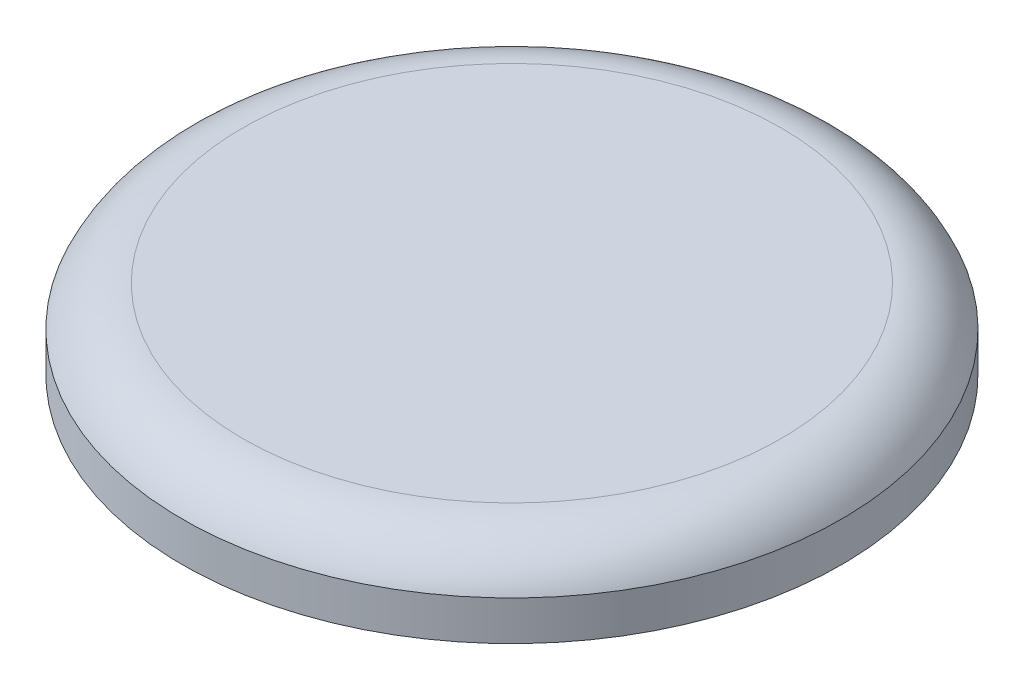
SolidWorks part; units mm, degrees
ref_plane "Front Plane" through (0, 0, 0) normal (0, 0, 1) x (1, 0, 0)
ref_plane "Top Plane" through (0, 0, 0) normal (0, 1, 0) x (1, 0, 0)
ref_plane "Right Plane" through (0, 0, 0) normal (1, 0, 0) x (0, 0, -1)
sketch "Sketch1" plane through (0, 0, 0) normal (0, 1, 0) x (1, 0, 0)
  circle A0 centre (0, 0) radius 25
  dimension "D1" = 50
extrude "Boss-Extrude1" add sketch "Sketch1" along normal blind 3
fillet "Fillet1" radius 5 1 edges at (0, 3, 25)
sketch "Sketch9" plane through (0, 0, 0) normal (0, -1, 0) x (1, 0, 0)
  circle A0 centre (0, 0) radius 25
  dimension "D1" = 50
extrude "Boss-Extrude2" add sketch "Sketch9" along normal blind 3
